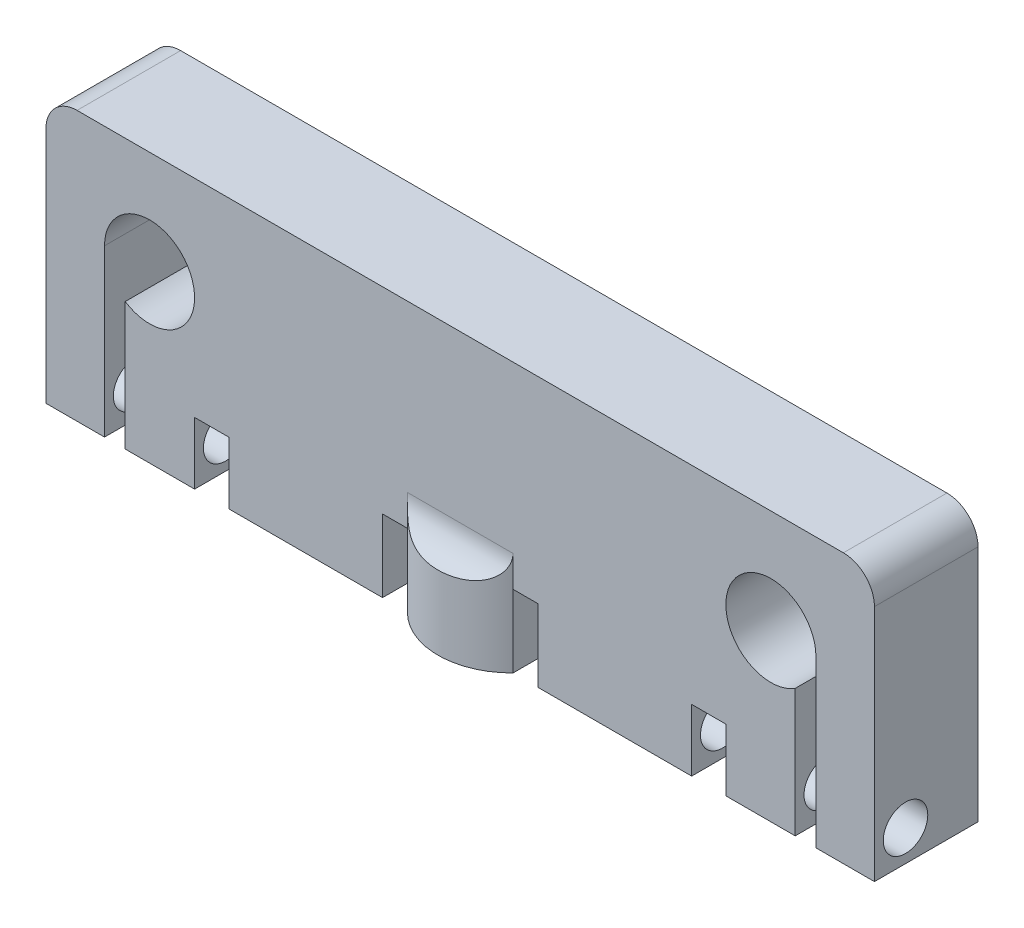
SolidWorks part; units mm, degrees
ref_plane "Front Plane" through (0, 0, 0) normal (0, 0, 1) x (1, 0, 0)
ref_plane "Top Plane" through (0, 0, 0) normal (0, 1, 0) x (1, 0, 0)
ref_plane "Right Plane" through (0, 0, 0) normal (1, 0, 0) x (0, 0, -1)
sketch "Sketch1" plane through (0, 0, 0) normal (0, 0, 1) x (1, 0, 0)
  line L0 (0, -16.0288) -> (0, 16.9064) construction
  line L1 (40, -13) -> (34.35, -13)
  line L2 (40, -13) -> (40, 13)
  line L3 (40, 13) -> (-40, 13)
  line L4 (-40, -13) -> (-40, 13)
  line L5 (40, -13) -> (34.35, -11.1638) construction
  line L6 (40, 13) -> (-32.35, -10.5138) construction
  line L7 (5.1, -6) -> (5.1, -13)
  line L8 (-7.5, -6) -> (-5.1, -6)
  line L9 (-7.5, -6) -> (-7.5, -13)
  line L11 (-5.1, -6) -> (-5.1, -13)
  line L12 (-7.5, -6) -> (-5.1, -13) construction
  line L13 (-7.5, -13) -> (-5.1, -6) construction
  line L14 (7.5, -6) -> (7.5, -13)
  line L15 (7.5, -6) -> (5.1, -6)
  line L16 (-7.5, -13) -> (-32.35, -13)
  line L17 (5.1, -13) -> (-5.1, -13)
  line L18 (-34.35, -13) -> (-40, -13)
  line L20 (-34.35, 3) -> (-34.35, -13)
  line L22 (-32.35, -0.6606) -> (-32.35, -13)
  line L23 (-34.35, -11.1638) -> (-40, -13) construction
  line L24 (32.35, -0.6606) -> (32.35, -13)
  line L25 (34.35, 3) -> (34.35, -13)
  line L26 (32.35, -13) -> (7.5, -13)
  line L27 (32.35, -10.5137) -> (-40, 13) construction
  arc A0 (-32.35, -0.6606) -> (-34.35, 3) centre (-30, 3) ccw
  arc A2 (32.35, -0.6606) -> (34.35, 3) centre (30, 3) cw
  point P0 (0, 0)
  point P13 (-6.3, -9.5)
  dimension "D3" = 8.7
  dimension "D1" = 80
  dimension "D2" = 26
  dimension "D4" = 10
  dimension "D5" = 10
  dimension "D6" = 7
  dimension "D7" = 2.4
  dimension "D8" = 6.3
  dimension "D9" = 2
extrude "Boss-Extrude1" add sketch "Sketch1" along normal mid plane 10
sketch "Sketch2" plane through (0, 0, 5) normal (0, 0, 1) x (1, 0, 0)
  line L5 (-40, 13) -> (-40, -13) construction
  line L6 (-25.65, -13) -> (-22.35, -13)
  line L7 (-25.65, -13) -> (-25.65, -7)
  line L8 (-25.65, -7) -> (-22.35, -7)
  line L9 (-22.35, -13) -> (-22.35, -7)
  line L10 (-25.65, -13) -> (-22.35, -7) construction
  line L11 (-25.65, -7) -> (-22.35, -13) construction
  line L12 (-32.35, -13) -> (-7.5, -13) construction
  line L13 (0, -16.0948) -> (0, 19.1324) construction
  line L14 (22.35, -13) -> (22.35, -7)
  line L15 (25.65, -13) -> (25.65, -7)
  line L16 (25.65, -7) -> (22.35, -7)
  line L17 (25.65, -13) -> (22.35, -13)
  point P0 (-24, -10)
  point P7 (-24, -13)
  dimension "D1" = 16
  dimension "D2" = 3.3
  dimension "D4" = 0
  dimension "D5" = 3
extrude "Cut-Extrude2" cut sketch "Sketch2" against normal blind 6.5 contours L7 L6 L9 L8 | L17 L14 L16 L15
sketch "Sketch3" plane through (-40, 0, 0) normal (-1, 0, 0) x (0, 0, 1)
  line L0 (5, -13) -> (-5, -13) construction
  line L1 (-5, 13) -> (-5, -13) construction
  circle A0 centre (2, -10) radius 2.15
  dimension "D1" = 4.3
  dimension "D2" = 3
  dimension "D3" = 7
extrude "Cut-Extrude4" cut sketch "Sketch3" against normal blind 24
mirror "Mirror1" about plane through (0, 0, 0) normal (1, 0, 0) of "Cut-Extrude4"
fillet "Fillet1" radius 0.5 2 edges at (5.1, -9.5, -5) (-5.1, -9.5, -5)
fillet "Fillet2" radius 3 2 edges at (40, 13, 0) (-40, 13, 0)
sketch "Sketch4" plane through (0, -13, 0) normal (0, -1, 0) x (1, 0, 0)
  line L0 (-5.1, 5) -> (5.1, 5) construction
  line L1 (-5.1, 5) -> (5.1, 5)
  arc A0 (-5.1, 5) -> (5.1, 5) centre (0, 0) cw
extrude "Boss-Extrude2" add sketch "Sketch4" against normal blind 7
fillet "Fillet3" radius 3 1 edges at (0, -6, 5)
